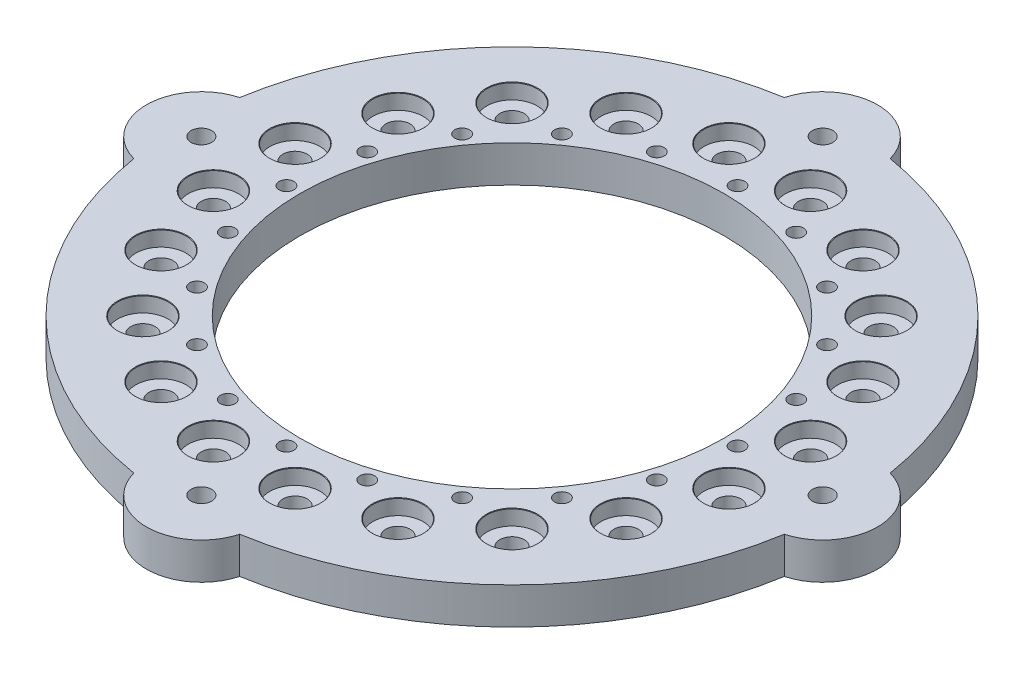
SolidWorks part; units mm, degrees
ref_plane "Front" through (0, 0, 0) normal (0, 0, 1) x (1, 0, 0)
ref_plane "Top" through (0, 0, 0) normal (0, 1, 0) x (1, 0, 0)
ref_plane "Right" through (0, 0, 0) normal (1, 0, 0) x (0, 0, -1)
sketch "Sketch3" plane through (0, 0, 0) normal (0, 1, 0) x (1, 0, 0)
  circle A0 centre (0, 0) radius 114.3
  circle A1 centre (0, 0) radius 73.533
  dimension "D1" = 147.066
  dimension "D2" = 228.6
extrude "Boss-Extrude1" add sketch "Sketch3" along normal blind 12.7
sketch "Sketch4" plane through (0, 12.7, 0) normal (0, 1, 0) x (1, 0, 0)
  circle A0 centre (0, 0) radius 89.8026
  circle A1 centre (0, 0) radius 78.232
  circle A2 centre (0, 0) radius 90.5256
  dimension "D1" = 181.0512
  dimension "D2" = 179.6051
  dimension "D3" = 156.464
ref_axis "Axis1" through (0, 12.7, 0) along (0, -1, 0)
sketch "Sketch7" plane through (0, 12.7, 0) normal (0, 1, 0) x (1, 0, 0)
  line L0 (0, 0) -> (177.5545, 0) construction
  line L1 (0, 0) -> (166.3309, 26.3442) construction
  line L2 (0, 0) -> (157.3635, 51.1305) construction
  dimension "D1" = 9
  dimension "D2" = 9
sketch "Sketch15" plane through (0, 12.7, 0) normal (0, 1, 0) x (1, 0, 0)
  line L0 (107.7631, 0) -> (0, 107.7631)
  line L1 (107.7631, 0) -> (0, -107.7631)
  line L2 (0, 107.7631) -> (-107.7631, 0)
  line L3 (0, -107.7631) -> (-107.7631, 0)
  line L4 (0, 0) -> (177.5545, 0) construction
  dimension "D1" = 152.4
  dimension "D2" = 152.4
  dimension "D3" = 76.2
  dimension "D4" = 76.2
sketch "Sketch16" plane through (0, 12.7, 0) normal (0, 1, 0) x (1, 0, 0)
  circle A0 centre (107.7631, 0) radius 19.05
  dimension "D1" = 38.1
extrude "Boss-Extrude2" add sketch "Sketch16" against normal blind 12.7
pattern_circular "CirPattern6" count 4 over 360 about axis through (0, 12.7, 0) along (0, -1, 0) of "Boss-Extrude2"
hole_wizard "CBORE for 5/16 Binding Head Machine Screw1" positions "Sketch9" profile "Sketch8" counterbore size "5/16" standard "ANSI Inch" end condition through all
sketch "Sketch9" plane through (0, 12.7, 0) normal (0, 1, 0) x (1, 0, 0)
  line L0 (0, 0) -> (166.3309, 26.3442) construction
  circle A0 centre (0, 0) radius 90.5256 construction
  point P0 (89.4111, 14.1613)
sketch "Sketch8" plane through (89.4111, 12.7, -14.1613) normal (1, 0, 0) x (0, 0, 1)
  line L0 (0, 0) -> (0, 12.7)
  line L1 (0, 12.7) -> (4.2164, 12.7)
  line L3 (4.2164, 12.7) -> (4.2164, 5.3086)
  line L4 (8.7312, 5.3086) -> (4.2164, 5.3086)
  line L5 (8.7312, 5.3086) -> (8.7312, 0.1587)
  line L6 (8.7312, 0.1587) -> (8.89, 0)
  line L7 (8.89, 0) -> (0, 0)
  line L8 (-8.7312, 0.1587) -> (-8.89, 0) construction
  line L11 (0, -6.35) -> (0, 107.95) construction
  dimension "Thru Hole Dia." = 8.4328
  dimension "Thru Hole Depth" = 12.7
  dimension "C'Bore Dia." = 17.4625
  dimension "C'Bore Depth" = 5.3086
  dimension "Near C'Sink Dia." = 17.78
  dimension "Near C'Sink Angle" = 90
pattern_circular "CirPattern2" count 20 over 360 about axis through (0, 12.7, 0) along (0, -1, 0) of "CBORE for 5/16 Binding Head Machine Screw1"
hole_wizard "1/4-20 Tapped Hole2" positions "Sketch13" profile "Sketch12" tap size "1/4-20" standard "ANSI Inch" end condition through all
sketch "Sketch13" plane through (0, 12.7, 0) normal (0, 1, 0) x (1, 0, 0)
  line L0 (0, 0) -> (177.5545, 0) construction
  circle A0 centre (0, 0) radius 78.232 construction
  point P0 (78.232, 0)
sketch "Sketch12" plane through (78.232, 12.7, 0) normal (1, 0, 0) x (0, 0, 1)
  line L0 (0, 0) -> (0, 12.7)
  line L1 (0, 12.7) -> (2.5527, 12.7)
  line L2 (2.5527, 12.7) -> (2.5527, 0)
  line L5 (2.5527, 0) -> (0, 0)
  line L11 (0, -6.35) -> (0, 107.95) construction
  dimension "Thru Tap Drill Dia." = 5.1054
  dimension "Thru Tap Drill Depth" = 12.7
cosmetic thread "Hole Thread2" parameters "D2"=6.35
pattern_circular "CirPattern4" count 20 over 360 about axis through (0, 12.7, 0) along (0, -1, 0) of "1/4-20 Tapped Hole2"
hole_wizard "CBORE for 1/4 Binding Head Machine Screw1" positions "Sketch20" profile "Sketch19" counterbore size "1/4" standard "ANSI Inch" end condition through all
sketch "Sketch20" plane through (0, 0, 0) normal (0, -1, 0) x (-1, 0, 0)
  point P0 (0, -107.7631)
  point P3 (-107.7631, 0)
  point P6 (0, 107.7631)
  point P9 (107.7631, 0)
sketch "Sketch19" plane through (0, 0, 107.7631) normal (1, 0, 0) x (0, 0, -1)
  line L0 (0, 0) -> (0, 12.7)
  line L1 (0, 12.7) -> (3.5712, 12.7)
  line L3 (3.5712, 12.7) -> (3.5712, 4.191)
  line L4 (7.1437, 4.191) -> (3.5712, 4.191)
  line L5 (7.1437, 4.191) -> (7.1437, 0.635)
  line L6 (7.1437, 0.635) -> (7.7788, 0)
  line L7 (7.7788, 0) -> (0, 0)
  line L8 (-7.1437, 0.635) -> (-7.7788, 0) construction
  line L11 (0, -6.35) -> (0, 107.95) construction
  dimension "Thru Hole Dia." = 7.1425
  dimension "Thru Hole Depth" = 12.7
  dimension "C'Bore Dia." = 14.2875
  dimension "C'Bore Depth" = 4.191
  dimension "Near C'Sink Dia." = 15.5575
  dimension "Near C'Sink Angle" = 90
